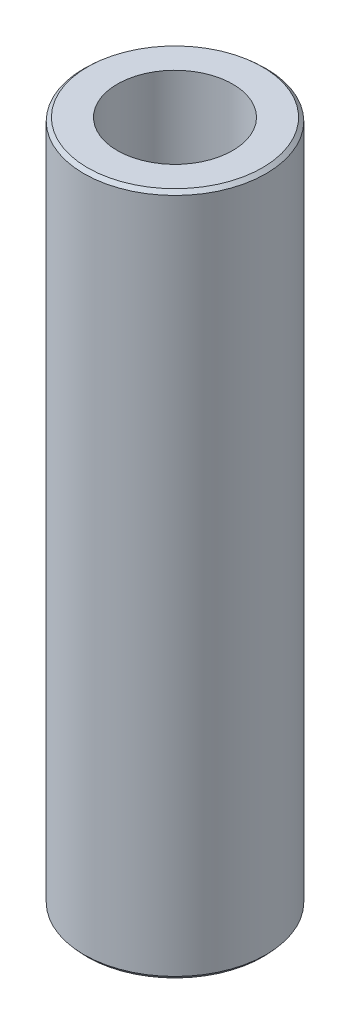
SolidWorks part; units mm, degrees
ref_plane "Front Plane" through (0, 0, 0) normal (0, 0, 1) x (1, 0, 0)
ref_plane "Top Plane" through (0, 0, 0) normal (0, 1, 0) x (1, 0, 0)
ref_plane "Right Plane" through (0, 0, 0) normal (1, 0, 0) x (0, 0, -1)
sketch "Sketch1" plane through (0, 0, 0) normal (0, 1, 0) x (1, 0, 0)
  circle A0 centre (0, 0) radius 35
  dimension "SHAFT_OD" = 70
extrude "Boss-Extrude1" add sketch "Sketch1" along normal blind 262.5876
sketch "Sketch2" plane through (0, 0, 0) normal (0, 1, 0) x (1, 0, 0)
  circle A0 centre (0, 0) radius 22.1571
  dimension "BORE_D" = 44.3141
extrude "Cut-Extrude1" cut sketch "Sketch2" along normal through all
chamfer "Chamfer1" distance 1.2654 angle 47.965 2 edges at (0, 262.5876, 35) (0, 0, 35) first distance on face at (0, 262.5876, 35) first distance on face at (0, 0, 22.1571)
